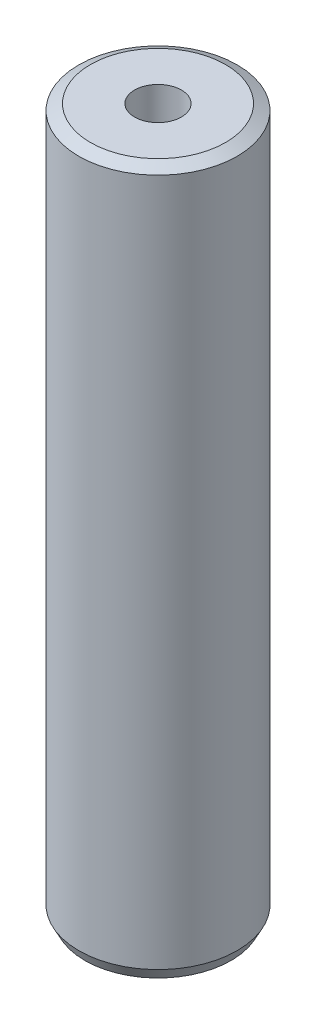
SolidWorks part; units mm, degrees
ref_plane "Front Plane" through (0, 0, 0) normal (0, 0, 1) x (1, 0, 0)
ref_plane "Top Plane" through (0, 0, 0) normal (0, 1, 0) x (1, 0, 0)
ref_plane "Right Plane" through (0, 0, 0) normal (1, 0, 0) x (0, 0, -1)
sketch "Sketch1" plane through (0, 0, 0) normal (0, 1, 0) x (1, 0, 0)
  circle A0 centre (0, 0) radius 52.5
  dimension "SHAFT_OD" = 105
extrude "Boss-Extrude1" add sketch "Sketch1" along normal blind 467.7919
sketch "Sketch2" plane through (0, 0, 0) normal (0, 1, 0) x (1, 0, 0)
  circle A0 centre (0, 0) radius 15.5239
  dimension "BORE_D" = 31.0478
extrude "Cut-Extrude1" cut sketch "Sketch2" along normal through all
chamfer "Chamfer1" distance 4.0325 angle 62.38 2 edges at (0, 467.7919, 52.5) (0, 0, 52.5) first distance on face at (0, 467.7919, 52.5) first distance on face at (0, 0, 15.5239)
